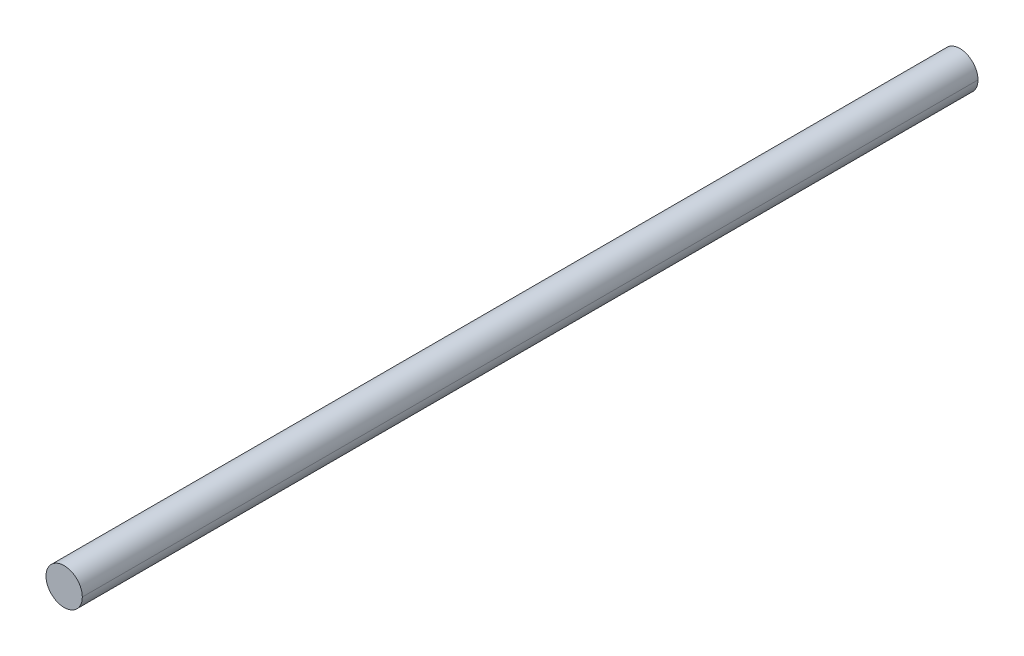
SolidWorks part; units mm, degrees
material "1.7036 (28CrS4)"
ref_plane "정면" through (0, 0, 0) normal (0, 0, 1) x (1, 0, 0)
ref_plane "윗면" through (0, 0, 0) normal (0, 1, 0) x (1, 0, 0)
ref_plane "우측면" through (0, 0, 0) normal (1, 0, 0) x (0, 0, -1)
sketch "스케치1" plane through (0, 0, 0) normal (0, 0, 1) x (1, 0, 0)
  circle A0 centre (0, 0) radius 5
  dimension "D1" = 10
extrude "보스-돌출1" add sketch "스케치1" along normal blind 218.44
sketch "스케치2" plane through (0, 0, 218.44) normal (0, 0, 1) x (1, 0, 0)
  text T0 "TEST\r\n"
sketch "스케치3" plane through (0, 0, 0) normal (0, 0, -1) x (-1, 0, 0)
  circle A0 centre (0, 0) radius 5
  dimension "D1" = 10
extrude "보스-돌출2" add sketch "스케치3" along normal blind 28.36
split line "분할선1"
equation "\"`\"=4"
